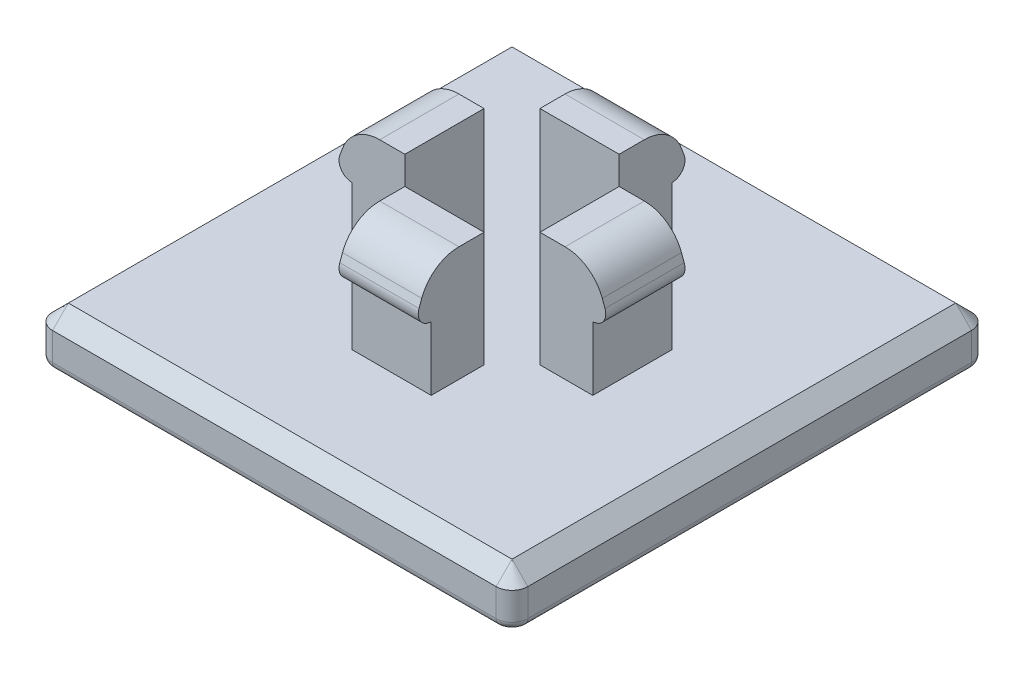
SolidWorks part; units mm, degrees
material "ABS"
ref_plane "Front Plane" through (0, 0, 0) normal (0, 0, 1) x (1, 0, 0)
ref_plane "Top Plane" through (0, 0, 0) normal (0, 1, 0) x (1, 0, 0)
ref_plane "Right Plane" through (0, 0, 0) normal (1, 0, 0) x (0, 0, -1)
sketch "Sketch1" plane through (0, 0, 0) normal (0, 1, 0) x (1, 0, 0)
  line L0 (-7.62, 7.112) -> (-7.62, -7.112)
  line L1 (-7.112, -7.62) -> (7.112, -7.62)
  line L2 (7.62, -7.112) -> (7.62, 7.112)
  line L3 (7.112, 7.62) -> (-7.112, 7.62)
  arc A0 (-7.62, -7.112) -> (-7.112, -7.62) centre (-7.112, -7.112) ccw
  arc A1 (7.112, -7.62) -> (7.62, -7.112) centre (7.112, -7.112) ccw
  arc A2 (7.62, 7.112) -> (7.112, 7.62) centre (7.112, 7.112) ccw
  arc A3 (-7.112, 7.62) -> (-7.62, 7.112) centre (-7.112, 7.112) ccw
  point P37 (0, 0)
  dimension "D1" = 0.508
extrude "Boss-Extrude1" add sketch "Sketch1" along normal blind 1.651
ref_plane "Plane1" through (0, 1.651, 0) normal (0, 1, 0) x (1, 0, 0)
sketch "Sketch3" plane through (0, 1.651, 0) normal (0, 1, 0) x (1, 0, 0)
  line L0 (-3.8605, 1.27) -> (-3.8605, -1.27)
  line L1 (-3.8605, -1.27) -> (-2.1657, -1.27)
  line L2 (-2.1657, -1.27) -> (-2.1657, 1.27)
  line L3 (-2.1657, 1.27) -> (-3.8605, 1.27)
  line L4 (1.27, 2.1657) -> (1.27, 3.8605)
  line L5 (1.27, 3.8605) -> (-1.27, 3.8605)
  line L6 (-1.27, 3.8605) -> (-1.27, 2.1657)
  line L7 (-1.27, 2.1657) -> (1.27, 2.1657)
  line L8 (2.1657, -1.27) -> (3.8605, -1.27)
  line L9 (3.8605, -1.27) -> (3.8605, 1.27)
  line L10 (3.8605, 1.27) -> (2.1657, 1.27)
  line L11 (2.1657, 1.27) -> (2.1657, -1.27)
  line L12 (-1.27, -2.1657) -> (-1.27, -3.8605)
  line L13 (-1.27, -3.8605) -> (1.27, -3.8605)
  line L14 (1.27, -3.8605) -> (1.27, -2.1657)
  line L15 (1.27, -2.1657) -> (-1.27, -2.1657)
  circle A0 centre (0, 0) radius 4.064
  point P22 (0, 0)
  dimension "D1" = 2.54
  dimension "D2" = 8.128
  dimension "D3" = 4
extrude "Boss-Extrude2" add sketch "Sketch3" along normal blind 3.683 contours L6 L7 L4 L5 | L10 L11 L8 L9 | L14 L15 L12 L13 | L2 L3 L0 L1 region at (-3.0131, 1.651, 0) region at (0, 1.651, -3.0131) region at (0, 1.651, 3.0131) region at (3.0131, 1.651, 0)
sketch "Sketch4" plane through (0, 0, 0) normal (0, 0, 1) x (1, 0, 0)
  line L0 (0, 7.0102) -> (0, 4.4783) construction
  line L1 (-3.8605, 5.334) -> (-4.2514, 4.2599)
  line L2 (3.8605, 5.334) -> (4.2514, 4.2599)
  line L4 (-3.8605, 5.334) -> (-3.8605, 1.651) construction
  line L5 (-3.8605, 3.7016) -> (-3.8605, 5.334)
  line L6 (3.8605, 3.7016) -> (3.8605, 5.334)
  arc A0 (-4.2514, 4.2599) -> (-3.8605, 3.7016) centre (-3.8605, 4.1176) ccw
  arc A1 (4.2514, 4.2599) -> (3.8605, 3.7016) centre (3.8605, 4.1176) cw
extrude "Boss-Extrude3" add sketch "Sketch4" along normal mid plane 2.54
sketch "Sketch5" plane through (0, 0, 0) normal (1, 0, 0) x (0, 0, -1)
  line L0 (0, 6.7375) -> (0, 2.9007) construction
  line L1 (-3.8605, 5.334) -> (-4.2514, 4.2599)
  line L2 (3.8605, 5.334) -> (4.2514, 4.2599)
  line L3 (-3.8605, 5.334) -> (-3.8605, 1.651) construction
  line L4 (-3.8605, 5.334) -> (-3.8605, 3.6992)
  line L5 (3.8605, 5.334) -> (3.8605, 3.6992)
  arc A0 (-4.2514, 4.2599) -> (-3.8605, 3.6992) centre (-3.8588, 4.117) ccw
  arc A1 (4.2514, 4.2599) -> (3.8605, 3.6992) centre (3.8588, 4.117) cw
extrude "Boss-Extrude4" add sketch "Sketch5" along normal mid plane 2.54
fillet "Fillet1" radius 1.27 4 edges at (0, 5.334, 3.8605) (3.8605, 5.334, 0) (0, 5.334, -3.8605) (-3.8605, 5.334, 0)
chamfer "Chamfer1" distance 0.508 angle 45 8 edges at (-7.62, 1.651, 0) (-7.4712, 1.651, 7.4712) (-7.4712, 1.651, -7.4712) (0, 1.651, 7.62) (0, 1.651, -7.62) (7.4712, 1.651, 7.4712) (7.4712, 1.651, -7.4712) (7.62, 1.651, 0)
fillet "Fillet2" radius 0.254 8 edges at (7.4712, 0, 7.4712) (0, 0, 7.62) (-7.4712, 0, 7.4712) (-7.62, 0, 0) (-7.4712, 0, -7.4712) (0, 0, -7.62) (7.4712, 0, -7.4712) (7.62, 0, 0)
